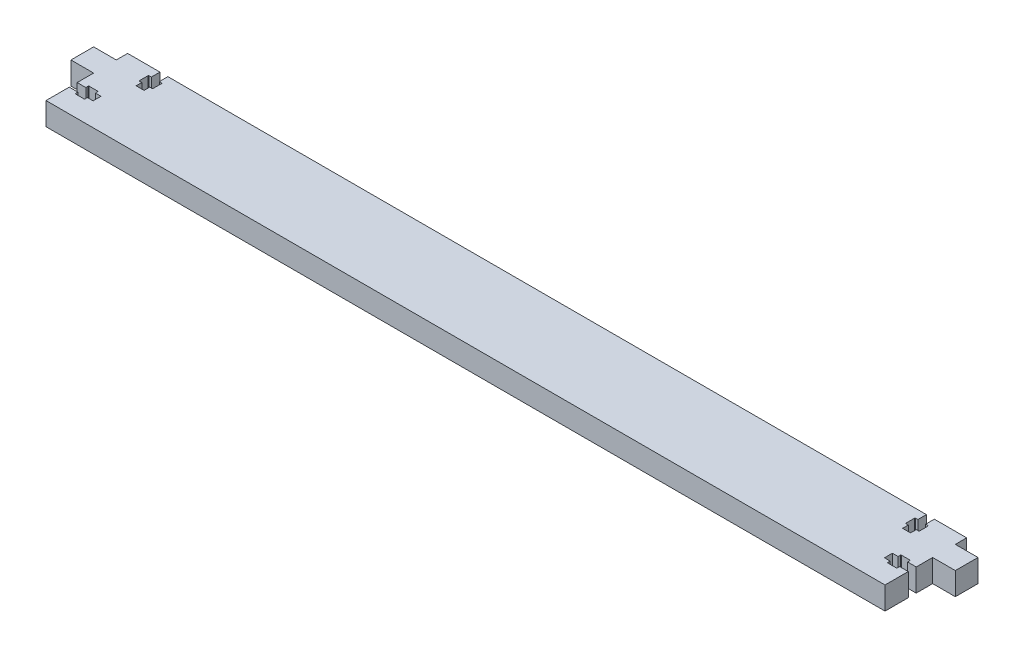
SolidWorks part; units mm, degrees
ref_plane "Front Plane" through (0, 0, 0) normal (0, 0, 1) x (1, 0, 0)
ref_plane "Top Plane" through (0, 0, 0) normal (0, 1, 0) x (1, 0, 0)
ref_plane "Right Plane" through (0, 0, 0) normal (1, 0, 0) x (0, 0, -1)
sketch "Sketch1" plane through (0, 0, 0) normal (0, 1, 0) x (1, 0, 0)
  line L0 (0, 18) -> (0, -18) construction
  line L1 (-185, 18) -> (0, 18)
  line L2 (-185, 18) -> (-185, 13)
  line L3 (-185, -18) -> (0, -18)
  line L4 (0, 18) -> (0, -18)
  line L5 (-185, 18) -> (0, 0) construction
  line L6 (-185, -18) -> (0, 0) construction
  line L7 (-185, 13) -> (-195, 13)
  line L8 (-195, 13) -> (-195, 3)
  line L9 (-195, 3) -> (-185, 3)
  line L10 (-185, 3) -> (-185, -18)
  point P0 (0, 0)
  dimension "D6" = 10
  dimension "D7" = 10
  dimension "D1" = 185
  dimension "D2" = 36
  dimension "D4" = 5
  dimension "D9" = 18
extrude "MainShape" add sketch "Sketch1" along normal blind 10 contours L2 L7 L8 L9 region at (-93.9423, 0, -0.1183)
sketch "Sketch2" plane through (0, 10, 0) normal (0, 1, 0) x (1, 0, 0)
  line L0 (-169, 18) -> (-169, 7.5) construction
  line L1 (-185, 18) -> (0, 18) construction
  line L2 (-170.75, 18) -> (-170.75, 14.2)
  line L3 (-170.75, 14.2) -> (-171.75, 14.2)
  line L4 (-172, 13.95) -> (-172, 10.25)
  line L5 (-171.75, 10) -> (-170.75, 10)
  line L6 (-170.75, 10) -> (-170.75, 7.5)
  line L7 (-170.75, 7.5) -> (-167.25, 7.5)
  line L8 (-185, 18) -> (-185, 13) construction
  line L9 (-170.75, 18) -> (-167.25, 18)
  line L10 (-167.25, 10) -> (-167.25, 7.5)
  line L11 (-166.25, 10) -> (-167.25, 10)
  line L12 (-166, 13.95) -> (-166, 10.25)
  line L13 (-167.25, 14.2) -> (-166.25, 14.2)
  line L14 (-167.25, 18) -> (-167.25, 14.2)
  line L16 (-185, -6) -> (-174.5, -6) construction
  line L50 (-185, 3) -> (-185, -18) construction
  line L51 (-174.5, -7.75) -> (-174.5, -4.25)
  line L52 (-174.5, -4.25) -> (-177, -4.25)
  line L53 (-177, -4.25) -> (-177, -3.25)
  line L54 (-177.25, -3) -> (-180.95, -3)
  line L55 (-181.2, -3.25) -> (-181.2, -4.25)
  line L56 (-181.2, -4.25) -> (-185, -4.25)
  line L57 (-185, -4.25) -> (-185, -7.75)
  line L58 (-195, 13) -> (-195, 3) construction
  line L59 (-181.2, -7.75) -> (-185, -7.75)
  line L60 (-181.2, -8.75) -> (-181.2, -7.75)
  line L61 (-177.25, -9) -> (-180.95, -9)
  line L62 (-177, -7.75) -> (-177, -8.75)
  line L63 (-174.5, -7.75) -> (-177, -7.75)
  arc A0 (-172, 10.25) -> (-171.75, 10) centre (-171.75, 10.25) ccw
  arc A1 (-171.75, 14.2) -> (-172, 13.95) centre (-171.75, 13.95) ccw
  arc A2 (-166.25, 14.2) -> (-166, 13.95) centre (-166.25, 13.95) cw
  arc A3 (-166, 10.25) -> (-166.25, 10) centre (-166.25, 10.25) cw
  arc A16 (-177, -3.25) -> (-177.25, -3) centre (-177.25, -3.25) ccw
  arc A17 (-180.95, -3) -> (-181.2, -3.25) centre (-180.95, -3.25) ccw
  arc A18 (-180.95, -9) -> (-181.2, -8.75) centre (-180.95, -8.75) cw
  arc A19 (-177, -8.75) -> (-177.25, -9) centre (-177.25, -8.75) cw
  point P14 (-172, 10)
  point P17 (-172, 14.2)
  point P28 (-166, 14.2)
  point P29 (-166, 10)
  point P34 (-195, 8)
  point P45 (-177, -3)
  point P48 (-181.2, -3)
  dimension "D8" = 0.25
  dimension "D16" = 0.25
  dimension "D1" = 10.5
  dimension "D2" = 1.75
  dimension "D3" = 1.75
  dimension "D4" = 8
  dimension "D5" = 3
  dimension "D6" = 4.2
  dimension "D7" = 16
  dimension "D9" = 10.5
  dimension "D10" = 8
  dimension "D11" = 4.2
  dimension "D12" = 3
  dimension "D13" = 1.75
  dimension "D14" = 1.75
  dimension "D15" = 14
extrude "ScrewSlots" cut sketch "Sketch2" against normal through all
mirror "Mirror1" about plane through (0, 0, 0) normal (1, 0, 0) of "ScrewSlots", "MainShape"
sketch "Sketch3" [suppressed] plane through (0, 10, 0) normal (0, 1, 0) x (1, 0, 0)
  line L0 (0, -18) -> (0, 18) construction
  line L1 (-180, -18) -> (180, -18) construction
  line L2 (-168.25, 18) -> (168.25, 18) construction
  line L3 (0, 18) -> (0, 58) construction
  line L4 (75, 58) -> (-75, 58)
  line L5 (-75, 58) -> (-115, 18)
  line L6 (-115, 18) -> (115, 18)
  line L7 (75, 58) -> (115, 18)
  line L8 (0, 0) -> (-180, -0.625) construction
  line L9 (-180, 3) -> (-180, -4.25) construction
  dimension "D1" = 40
  dimension "D2" = 45
  dimension "D3" = 75
extrude "ExpandedPiece" [suppressed] add sketch "Sketch3" against normal up to surface (10 mm away) up to face at (0, 0, -3.4789)
sketch "Sketch5" [suppressed] plane through (0, 10, 0) normal (0, 1, 0) x (1, 0, 0)
  line L0 (0, 58) -> (0, -18) construction
  line L1 (75, 58) -> (-75, 58) construction
  line L2 (-180, -18) -> (180, -18) construction
  line L3 (72.5, 53) -> (-72.5, 53) construction
  line L4 (72.5, 3.2) -> (-72.5, 3.2) construction
  line L5 (-72.5, 53) -> (-72.5, 3.2) construction
  line L6 (72.5, 53) -> (72.5, 3.2) construction
  line L7 (-72.5, 53) -> (-72.5, 3.2) construction
  circle A0 centre (-72.5, 53) radius 1.6
  circle A1 centre (-72.5, 3.2) radius 1.6
  circle A2 centre (72.5, 3.2) radius 1.6
  circle A3 centre (72.5, 53) radius 1.6
  point P13 (0, 53)
  point P14 (0, 3.2)
  dimension "D1" = 3.2
  dimension "D4" = 3.2
  dimension "D2" = 72.5
  dimension "D3" = 49.8
  dimension "D5" = 5
extrude "ScrewHoles" [suppressed] cut sketch "Sketch5" against normal through all
sketch "Sketch4" [suppressed] plane through (0, 10, 0) normal (0, 1, 0) x (1, 0, 0)
  line L0 (-14.8311, -18) -> (-14.8311, 58) construction
  line L1 (-180, -18) -> (180, -18) construction
  line L2 (75, 58) -> (-75, 58) construction
  line L4 (-62.3311, 3.2) -> (32.6689, 3.2)
  line L5 (-62.3311, 3.2) -> (-62.3311, 43.7)
  line L6 (-62.3311, 43.7) -> (32.6689, 43.7)
  line L7 (32.6689, 3.2) -> (32.6689, 43.7)
  line L8 (-62.3311, 3.2) -> (32.6689, 43.7) construction
  line L9 (-62.3311, 43.7) -> (32.6689, 3.2) construction
  circle A0 centre (72.5, 53) radius 1.6 construction
  circle A1 centre (72.5, 3.2) radius 1.6 construction
  point P6 (-14.8311, 23.45)
  dimension "D1" = 95
  dimension "D2" = 40.5
  dimension "D3" = 39.8311
  dimension "D4" = 0
equation "\"Y-ROD-SPACING\"=75"
equation "\"Y-BED-OFFSET\"=2"
equation "\"Y-BED-ROD-INSET\"=3.5"
equation "\"T-SLOT-NUT-FILLET-RADIUS\"=0.25"
equation "\"T-SLOT-SCREW-SHAFT-RADIUS\"=1.75"
equation "\"T-SLOT-SCREW-SHAFT-CUTOUT-LENGTH\"=10.5"
equation "\"T-SLOT-NUT-DEPTH\"=4.2"
equation "\"T-SLOT-NUT-WIDTH\"=3"
equation "\"T-SLOT-NUT-END-DISTANCE\"=8"
equation "\"ACRYLIC-TAB-CUTOUT-SIZE\"=\"ACRYLIC-THICKNESS\"+\"ACRYLIC-TAB-TOLERANCE\"*2"
equation "\"ACRYLIC-M3-HOLE\"=3.2"
equation "\"SMOOTHROD-CAP-SCREW-DISTANCE\"=20"
equation "\"D2@Sketch2\"=\"T-SLOT-SCREW-SHAFT-RADIUS\""
equation "\"D1@Sketch2\"=\"T-SLOT-SCREW-SHAFT-CUTOUT-LENGTH\""
equation "\"D6@Sketch2\"=\"T-SLOT-NUT-DEPTH\""
equation "\"D5@Sketch2\"=\"T-SLOT-NUT-WIDTH\""
equation "\"D3@Sketch2\"=\"T-SLOT-SCREW-SHAFT-RADIUS\""
equation "\"D8@Sketch2\"=\"T-SLOT-NUT-FILLET-RADIUS\""
equation "\"D4@Sketch2\"=\"T-SLOT-NUT-END-DISTANCE\""
equation "\"D11@Sketch2\"=\"T-SLOT-NUT-DEPTH\""
equation "\"D10@Sketch2\"=\"T-SLOT-NUT-END-DISTANCE\""
equation "\"D13@Sketch2\"=\"T-SLOT-SCREW-SHAFT-RADIUS\""
equation "\"D14@Sketch2\"=\"T-SLOT-SCREW-SHAFT-RADIUS\""
equation "\"D16@Sketch2\"=\"T-SLOT-NUT-FILLET-RADIUS\""
equation "\"D9@Sketch2\"=\"T-SLOT-SCREW-SHAFT-CUTOUT-LENGTH\""
equation "\"ACRYLIC-TAB-WIDTH\"=\"ACRYLIC-THICKNESS\""
equation "\"D6@Sketch1\"=\"ACRYLIC-TAB-WIDTH\""
equation "\"D7@Sketch1\"=\"ACRYLIC-TAB-WIDTH\""
equation "\"FRAME-WIDTH-INNER\"=370"
equation "\"D1@Sketch1\"=\"FRAME-WIDTH-INNER\"/2"
equation "\"X-ROD-SPACING\"=45"
equation "\"Z-ROD-SPACING\"=17.5"
equation "\"ACRYLIC-THICKNESS\"=10"
equation "\"ACRYLIC-THICKNESS2\"=4.5"
equation "\"NEMA17-HOLE-SPACING\"=31"
equation "\"NEMA17-CENTRAL-CUTOUT\"=22.5"
equation "\"Z-BRACKET-REACH\"=55"
equation "\"TOP-BRACKET-SPACING\"=40"
equation "\"SMOOTHROD-X-LENGTH\"=350"
equation "\"SMOOTHROD-Y-LENGTH\"=350"
equation "\"SMOOTHROD-Z-LENGTH\"=350"
equation "\"SMOOTHROD-TIGHTENING-HEADROOM\"=1"
equation "\"LEADSCREW-Z-LENGTH\"=300"
equation "\"SCREW-LENGTH-FRAME\"=\"ACRYLIC-THICKNESS\" + 10"
equation "\"SCREW-HEAD-RADIUS\"=6"
equation "\"PRINTED-X-SMOOTHROD-DIAMETER\"=8.2"
equation "\"PRINTED-X-SMOOTHROD-CUTOUT\"=10"
equation "\"PRINTED-X-BASE-HEIGHT\"=10"
equation "\"PRINTED-LM8UU-CUTOUT-SIZE\"=16"
equation "\"PRINTED-LM8UU-CUTOUT-LENGTH\"=24.5"
equation "\"PRINTED-X-IDLER-HEIGHT\"=16"
equation "\"PSU-MOUNTING-WIDTH\"=95"
equation "\"PSU-MOUNTING-HEIGHT\"=177"
equation "\"D1@MainShape\"=\"ACRYLIC-THICKNESS\""
equation "\"D1@Sketch5\"=\"ACRYLIC-M3-HOLE\""
equation "\"D4@Sketch5\"=\"ACRYLIC-M3-HOLE\""
equation "\"Y-BELT-TO-ROD-DISTANCE\"=20"
equation "\"SPOOL-HOLDER-ROD-SPACING\"=150"
equation "\"Z-ROD-INSET\"=16"
equation "\"D7@Sketch2\"=\"Z-ROD-INSET\""
